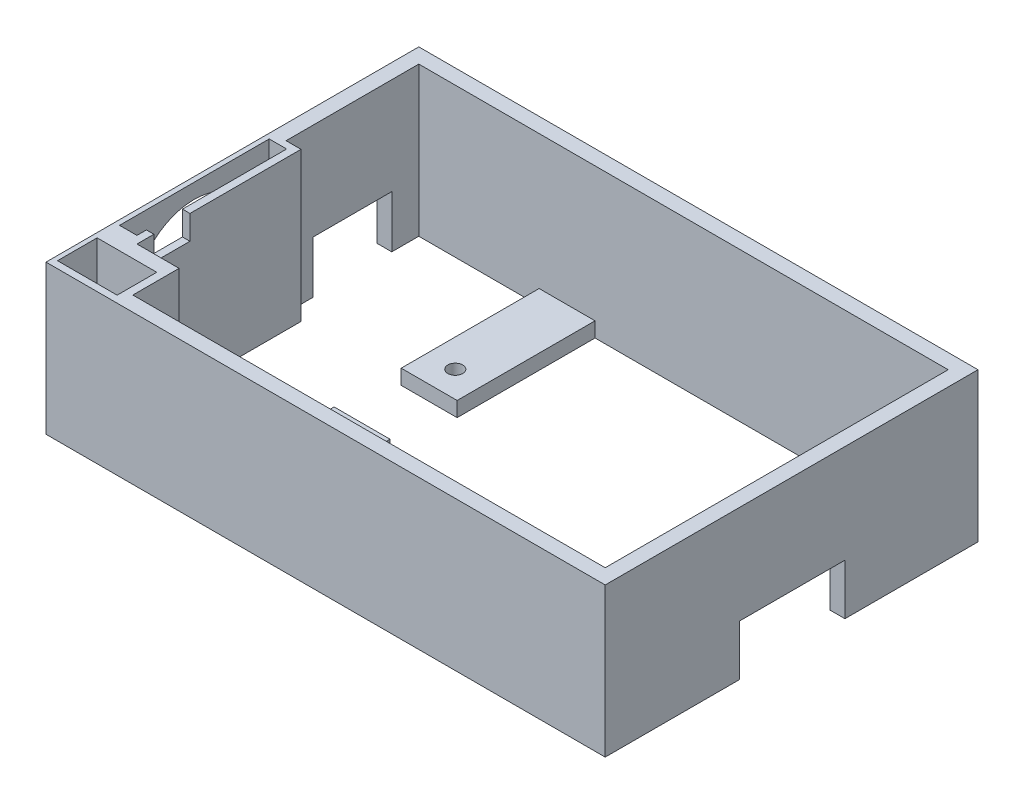
SolidWorks part; units mm, degrees
ref_plane "Front Plane" through (0, 0, 0) normal (0, 0, 1) x (1, 0, 0)
ref_plane "Top Plane" through (0, 0, 0) normal (0, 1, 0) x (1, 0, 0)
ref_plane "Right Plane" through (0, 0, 0) normal (1, 0, 0) x (0, 0, -1)
sketch "Sketch1" plane through (0, 0, 0) normal (0, 1, 0) x (1, 0, 0)
  line L1 (0, 0) -> (150, 0)
  line L2 (0, 0) -> (0, 100)
  line L3 (0, 100) -> (150, 100)
  line L4 (150, 0) -> (150, 100)
  line L5 (4, 96) -> (146, 96)
  line L6 (4, 96) -> (4, 4)
  line L7 (4, 4) -> (146, 4)
  line L8 (146, 96) -> (146, 4)
  dimension "D1" = 4
  dimension "D2" = 4
  dimension "D3" = 4
  dimension "D4" = 4
  dimension "D5" = 150
  dimension "D6" = 100
extrude "Boss-Extrude1" add sketch "Sketch1" along normal blind 40
sketch "Sketch10" plane through (4, 0, 0) normal (1, 0, 0) x (0, 0, -1)
  line L0 (96, 0) -> (4, 0) construction
  line L1 (18.3994, 0) -> (58.3994, 0)
  line L2 (18.3994, 0) -> (18.3994, 40)
  line L3 (18.3994, 40) -> (58.3994, 40)
  line L4 (58.3994, 0) -> (58.3994, 40)
  line L5 (96, 40) -> (4, 40) construction
  circle A0 centre (38.3994, 20) radius 20
  circle A1 centre (38.3994, 20) radius 16
  dimension "D1" = 40
sketch "Sketch11" plane through (4, 0, 0) normal (1, 0, 0) x (0, 0, -1)
  line L0 (18.3994, 0) -> (16.3994, 0)
  line L1 (96, 0) -> (4, 0) construction
  line L2 (16.3994, 0) -> (16.3994, 40)
  line L3 (96, 40) -> (4, 40) construction
  line L4 (16.3994, 40) -> (18.3994, 40)
  line L5 (18.3994, 40) -> (18.3994, 0)
  line L6 (58.3994, 0) -> (58.3994, 40)
  line L7 (58.3994, 40) -> (60.3994, 40)
  line L8 (60.3994, 40) -> (60.3994, 0)
  line L9 (60.3994, 0) -> (58.3994, 0)
extrude "Boss-Extrude5" add sketch "Sketch11" along normal blind 4
sketch "Sketch12" plane through (0, 0, -18.3994) normal (0, 0, -1) x (-1, 0, 0)
  line L0 (-8, 0) -> (-4, 0) construction
  line L1 (-8, 40) -> (-6, 40)
  line L2 (-8, 40) -> (-8, 0)
  line L3 (-8, 0) -> (-6, 0)
  line L4 (-6, 40) -> (-6, 0)
extrude "Boss-Extrude6" add sketch "Sketch12" along normal up to surface (42 mm away) up to face at (6, 20, -60.3994)
sketch "Sketch13" plane through (0, 40, 0) normal (0, 1, 0) x (1, 0, 0)
  line L0 (0, 100) -> (0, 0) construction
  line L1 (6, 18.3994) -> (1.32, 18.3994)
  line L2 (6, 18.3994) -> (6, 58.5494)
  line L3 (6, 58.5494) -> (1.32, 58.5494)
  line L4 (1.32, 18.3994) -> (1.32, 58.5494)
  line L5 (6, 58.3994) -> (6, 18.3994) construction
  line L6 (8, 60.3994) -> (8, 16.3994) construction
  dimension "D1" = 4.68
  dimension "D2" = 40.15
  dimension "D3" = 1.32
  dimension "D4" = 2
extrude "Cut-Extrude4" cut sketch "Sketch13" against normal up to surface (40 mm away) up to face at (5, 0, -38.3994)
extrude "Cut-Extrude5" cut sketch "Sketch10" against normal blind 42 contours A1 region at (4, 20, -38.3994)
sketch "Sketch14" plane through (0, 0, 0) normal (0, -1, 0) x (-1, 0, 0)
  line L0 (-4, 4) -> (-146, 4) construction
  line L1 (-36.279, 4) -> (-51.279, 4)
  line L2 (-36.279, 4) -> (-36.279, 41)
  line L3 (-36.279, 41) -> (-51.279, 41)
  line L4 (-51.279, 4) -> (-51.279, 41)
  line L5 (-146, 96) -> (-4, 96) construction
  line L6 (-36.279, 96) -> (-51.279, 96)
  line L7 (-36.279, 96) -> (-36.279, 59)
  line L8 (-36.279, 59) -> (-51.279, 59)
  line L9 (-51.279, 96) -> (-51.279, 59)
  line L11 (-127.5398, 96) -> (-112.5398, 96)
  line L12 (-127.5398, 96) -> (-127.5398, 59)
  line L13 (-127.5398, 59) -> (-112.5398, 59)
  line L14 (-112.5398, 96) -> (-112.5398, 59)
  line L21 (-127.5398, 4) -> (-112.5398, 4)
  line L22 (-127.5398, 4) -> (-127.5398, 41)
  line L23 (-127.5398, 41) -> (-112.5398, 41)
  line L24 (-112.5398, 4) -> (-112.5398, 41)
  circle A4 centre (-43.779, 34) radius 2
  circle A6 centre (-43.779, 66) radius 2
  circle A7 centre (-120.0398, 65.2431) radius 2
  circle A8 centre (-120.0398, 34) radius 2
  dimension "D8" = 15
  dimension "D4" = 7
  dimension "D1" = 37
  dimension "D2" = 15
  dimension "D3" = 37
  dimension "D5" = 7
  dimension "D7" = 37
sketch "Sketch15" plane through (4, 0, 0) normal (1, 0, 0) x (0, 0, -1)
  line L0 (96, 0) -> (60.3994, 0) construction
  line L2 (67.65, 0) -> (67.65, 14)
  line L3 (67.65, 14) -> (88.75, 14)
  line L4 (88.75, 0) -> (88.75, 14)
  line L5 (96, 40) -> (96, 0) construction
  line L9 (67.65, 0) -> (88.75, 0)
  line L11 (60.3994, 0) -> (60.3994, 40) construction
  line L12 (60.3994, 0) -> (60.3994, 40) construction
  point P12 (60.3994, 0)
  dimension "D1" = 21.1
  dimension "D2" = 14
  dimension "D3" = 7.25
  dimension "D4" = 7.2506
  dimension "D5" = 35.6006
extrude "Cut-Extrude6" cut sketch "Sketch15" against normal blind 10
extrude "Boss-Extrude7" add sketch "Sketch14" against normal blind 4
sketch "Sketch16" plane through (150, 0, 0) normal (1, 0, 0) x (0, 0, -1)
  line L0 (0, 0) -> (100, 0) construction
  line L1 (36.0481, 0) -> (64.3045, 0)
  line L2 (36.0481, 0) -> (36.0481, 13.6043)
  line L3 (36.0481, 13.6043) -> (64.3045, 13.6043)
  line L4 (64.3045, 0) -> (64.3045, 13.6043)
extrude "Cut-Extrude7" cut sketch "Sketch16" against normal up to surface (4 mm away) up to face at (146, 20, -50)
sketch "Sketch17" plane through (0, 40, 0) normal (0, 1, 0) x (1, 0, 0)
  line L0 (4, 4) -> (146, 4) construction
  line L1 (4, 16.3994) -> (19.3, 16.3994)
  line L2 (4, 16.3994) -> (4, 4)
  line L3 (4, 4) -> (19.3, 4)
  line L4 (19.3, 16.3994) -> (19.3, 4)
  dimension "D1" = 15.3
extrude "Boss-Extrude8" add sketch "Sketch17" against normal up to surface (40 mm away) up to face at (78.4547, 0, -82.3818)
sketch "Sketch18" plane through (0, 40, 0) normal (0, 1, 0) x (1, 0, 0)
  line L1 (1.22, 1.8626) -> (17.22, 1.8626)
  line L2 (1.22, 1.8626) -> (1.22, 12.4926)
  line L3 (1.22, 12.4926) -> (17.22, 12.4926)
  line L4 (17.22, 1.8626) -> (17.22, 12.4926)
  dimension "D1" = 16
  dimension "D2" = 10.63
extrude "Cut-Extrude8" cut sketch "Sketch18" against normal blind 20
sketch "Sketch19" plane through (0, 0, -12.4926) normal (0, 0, 1) x (1, 0, 0)
  line L0 (17.22, 20) -> (1.22, 20) construction
  line L1 (11.2343, 20) -> (16.1452, 20)
  line L2 (11.2343, 20) -> (11.2343, 30)
  line L3 (11.2343, 30) -> (16.1452, 30)
  line L4 (16.1452, 20) -> (16.1452, 30)
extrude "Cut-Extrude9" cut sketch "Sketch19" against normal blind 20
sketch "Sketch20" plane through (8, 0, 0) normal (1, 0, 0) x (0, 0, -1)
  line L0 (60.3994, 40) -> (16.3994, 40) construction
  line L1 (20.9377, 40) -> (30.6084, 40)
  line L2 (20.9377, 40) -> (20.9377, 33.5357)
  line L3 (20.9377, 33.5357) -> (30.6084, 33.5357)
  line L4 (30.6084, 40) -> (30.6084, 33.5357)
extrude "Cut-Extrude10" cut sketch "Sketch20" against normal blind 4
sketch "Sketch21" plane through (0, 40, 0) normal (0, 1, 0) x (1, 0, 0)
  line L0 (8, 16.3994) -> (0, 16.3994)
  line L1 (0, 100) -> (0, 0) construction
  line L2 (0, 16.3994) -> (19.3, 16.3994)
  line L3 (19.3, 16.3994) -> (19.3, 0)
  line L4 (0, 0) -> (150, 0) construction
  dimension "D1" = 19.3
  dimension "D2" = 16.3994
